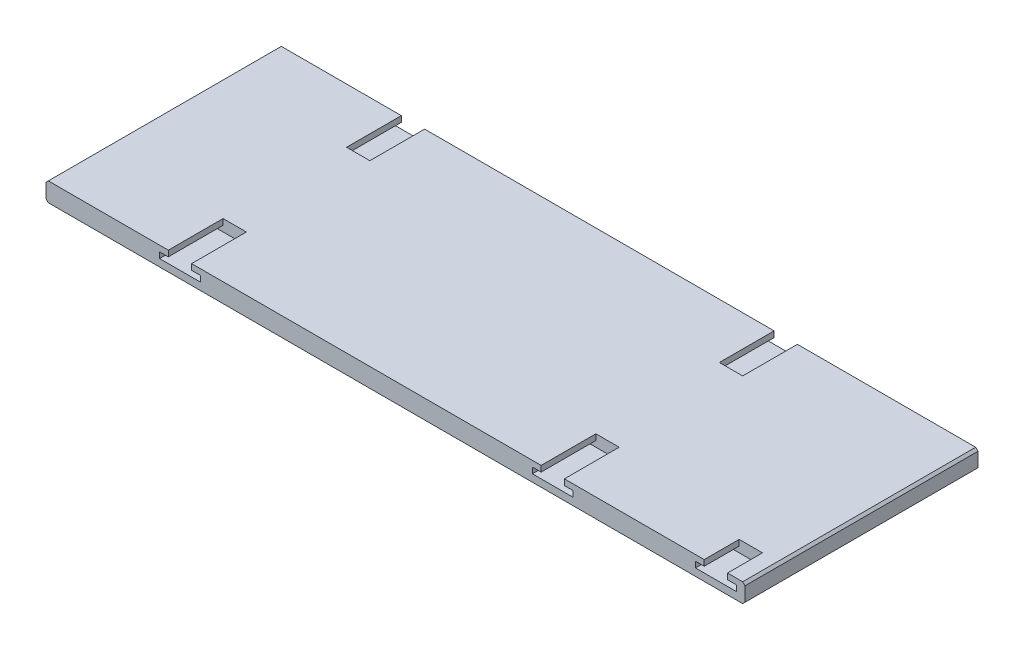
SolidWorks part; units mm, degrees
note: The reader was unsure of these and kept them because the rebuilt part matched: shared geometry of "Esquisse1<4>", "Esquisse1<5>", "Esquisse1<9>".
ref_plane "Plan de face" through (0, 0, 0) normal (0, 0, 1) x (1, 0, 0)
ref_plane "Plan de dessus" through (0, 0, 0) normal (0, 1, 0) x (1, 0, 0)
ref_plane "Plan de droite" through (0, 0, 0) normal (1, 0, 0) x (0, 0, -1)
sketch "Esquisse1" plane through (0, 0, 0) normal (0, 0, 1) x (1, 0, 0)
  line L0 (275, 59.2537) -> (275, -36.2234) construction
  line L1 (0, 0) -> (600, 0)
  line L2 (0, 0) -> (0, 16.28)
  line L3 (0, 16.28) -> (105, 16.28)
  line L4 (600, 0) -> (600, 16.28)
  line L5 (115, 59.2537) -> (115, -40.5432) construction
  line L6 (435, 59.2537) -> (435, -40.5432) construction
  line L7 (275, 59.2537) -> (275, -58.1656) construction
  line L8 (585, 16.28) -> (585, 11.28)
  line L9 (105, 16.28) -> (105, 11.28)
  line L10 (105, 11.28) -> (97.5, 11.28)
  line L11 (97.5, 11.28) -> (97.5, 6.28)
  line L12 (97.5, 6.28) -> (132.5, 6.28)
  line L13 (132.5, 11.28) -> (132.5, 6.28)
  line L14 (125, 11.28) -> (132.5, 11.28)
  line L15 (125, 16.28) -> (125, 11.28)
  line L16 (425, 16.28) -> (425, 11.28)
  line L17 (425, 11.28) -> (417.5, 11.28)
  line L18 (417.5, 11.28) -> (417.5, 6.28)
  line L19 (452.5, 6.28) -> (417.5, 6.28)
  line L20 (452.5, 11.28) -> (452.5, 6.28)
  line L21 (445, 11.28) -> (452.5, 11.28)
  line L22 (445, 16.28) -> (445, 11.28)
  line L23 (125, 16.28) -> (425, 16.28)
  line L24 (445, 16.28) -> (600, 16.28)
  line L25 (105, 16.28) -> (125, 16.28)
  line L26 (425, 16.28) -> (445, 16.28)
  line L27 (585, 11.28) -> (592.5, 11.28)
  line L36 (115, 59.2537) -> (115, -58.1656) construction
  line L37 (592.5, 11.28) -> (592.5, 6.28)
  line L38 (592.5, 6.28) -> (557.5, 6.28)
  line L39 (557.5, 11.28) -> (557.5, 6.28)
  line L40 (565, 11.28) -> (557.5, 11.28)
  line L41 (565, 16.28) -> (565, 11.28)
  point P12 (575, 6.28)
  point P21 (115, 6.28)
  point P32 (435, 6.28)
  dimension "D2" = 16.28
  dimension "D3" = 275
  dimension "D8" = 5
  dimension "D9" = 7.5
  dimension "D10" = 17.5
  dimension "D11" = 5
  dimension "D7" = 600
  dimension "D5" = 2
  dimension "D6" = 140
  dimension "D4" = 160
extrude "Boss.-Extru.1" add sketch "Esquisse1" along normal mid plane 200
chamfer "Chanfrein1" distance 2 angle 45 4 edges at (600, 16.28, 0) (0, 16.28, 0) (600, 0, 0) (0, 0, 0)
extrude "Enlèv. mat.-Extru.1" cut sketch "Esquisse1<4>" against normal through all from offset 53 contours L25 L9 L10 L11 L12 L13 L14 L15 | L26 L16 L17 L18 L19 L20 L21 L22 offset against normal yes
sketch "Esquisse1<4>" plane through (0, 0, 0) normal (0, 0, 1) x (1, 0, 0) same geometry as "Esquisse1"
extrude "Enlèv. mat.-Extru.2" cut sketch "Esquisse1<5>" along normal through all from offset 53 contours L25 L9 L10 L11 L12 L13 L14 L15 | L26 L16 L17 L18 L19 L20 L21 L22
sketch "Esquisse1<5>" plane through (0, 0, 0) normal (0, 0, 1) x (1, 0, 0) same geometry as "Esquisse1"
extrude "Enlèv. mat.-Extru.4" cut sketch "Esquisse1<9>" against normal blind 30 from offset 100 contours L24 L41 L40 L39 L38 L37 L27 L8
sketch "Esquisse1<9>" plane through (0, 0, 0) normal (0, 0, 1) x (1, 0, 0) same geometry as "Esquisse1"
